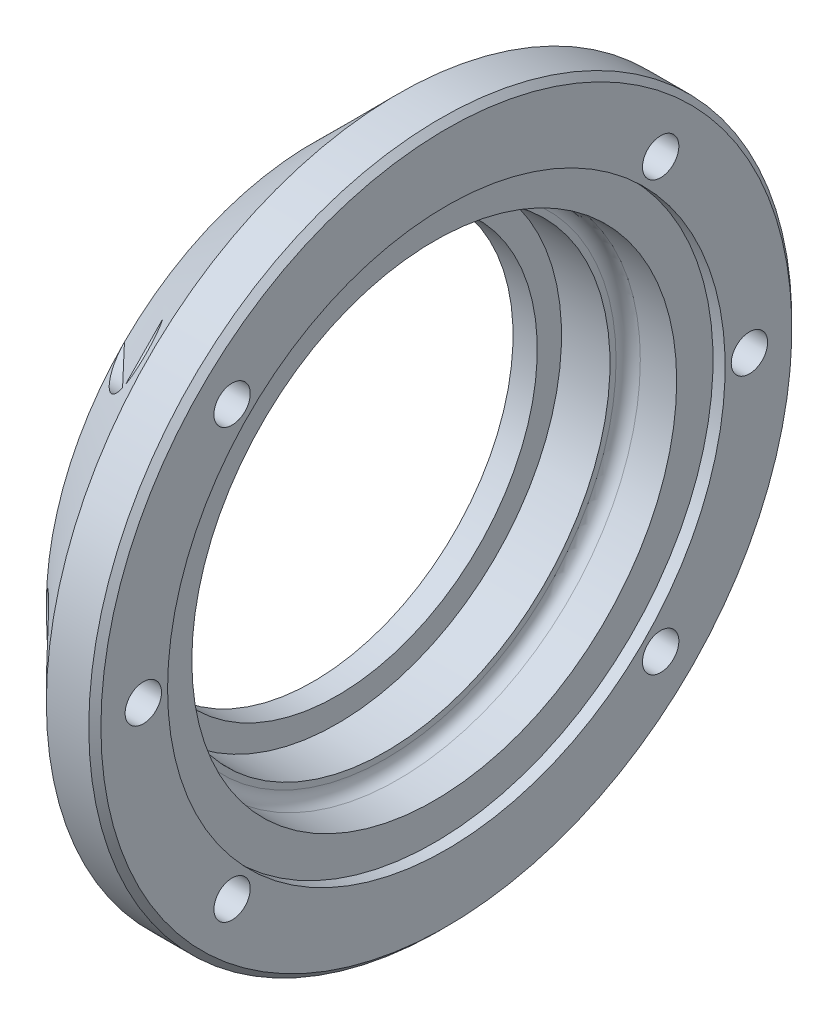
SolidWorks part; units mm, degrees
material "ABS"
ref_plane "Front" through (0, 0, 0) normal (0, 0, 1) x (1, 0, 0)
ref_plane "Top" through (0, 0, 0) normal (0, 1, 0) x (1, 0, 0)
ref_plane "Right" through (0, 0, 0) normal (1, 0, 0) x (0, 0, -1)
sketch "Szkic2" plane through (0, 0, 0) normal (0, 1, 0) x (1, 0, 0)
  line L42 (7, 20) -> (10, 20)
  line L43 (2, 18.5) -> (2, 16.5)
  line L46 (2, 18.5) -> (6, 18.5)
  line L48 (11, 23) -> (11, 28.5)
  line L49 (7, 29) -> (0, 22)
  line L50 (7, 29) -> (10.5, 29)
  line L51 (11, 28.5) -> (10.5, 29)
  line L53 (11, 23) -> (10, 23)
  line L54 (10, 20) -> (10, 23)
  line L55 (6, 18.5) -> (6, 19)
  line L56 (0, 16.5) -> (0, 22)
  line L58 (2, 16.5) -> (0, 16.5)
  line L118 (0, 0) -> (9.0917, 0) construction
  arc A5 (7, 20) -> (6, 19) centre (7, 19) ccw
  dimension "D1" = 16.5
revolve "Obrót1" add sketch "Szkic2" angle 360 about L118
sketch "Szkic3" plane through (0, 0, 0) normal (-1, 0, 0) x (0, 0, 1)
  circle A1 centre (17.6777, 17.6777) radius 3
  circle A2 centre (25, 0) radius 3
  circle A3 centre (17.6777, -17.6777) radius 3
  circle A5 centre (-17.6777, -17.6777) radius 3
  circle A6 centre (-25, 0) radius 3
  circle A7 centre (-17.6777, 17.6777) radius 3
  point P19 (0, 0)
extrude "Wytnij-wyciągnięcie1" cut sketch "Szkic3" against normal blind 7
sketch "Szkic4" plane through (0, 0, 0) normal (-1, 0, 0) x (0, 0, 1)
  circle A1 centre (17.6777, 17.6777) radius 1.5
  circle A2 centre (25, 0) radius 1.5
  circle A3 centre (17.6777, -17.6777) radius 1.5
  circle A5 centre (-17.6777, -17.6777) radius 1.5
  circle A6 centre (-25, 0) radius 1.5
  circle A7 centre (-17.6777, 17.6777) radius 1.5
  point P19 (0, 0)
extrude "Wytnij-wyciągnięcie2" cut sketch "Szkic4" against normal through all
